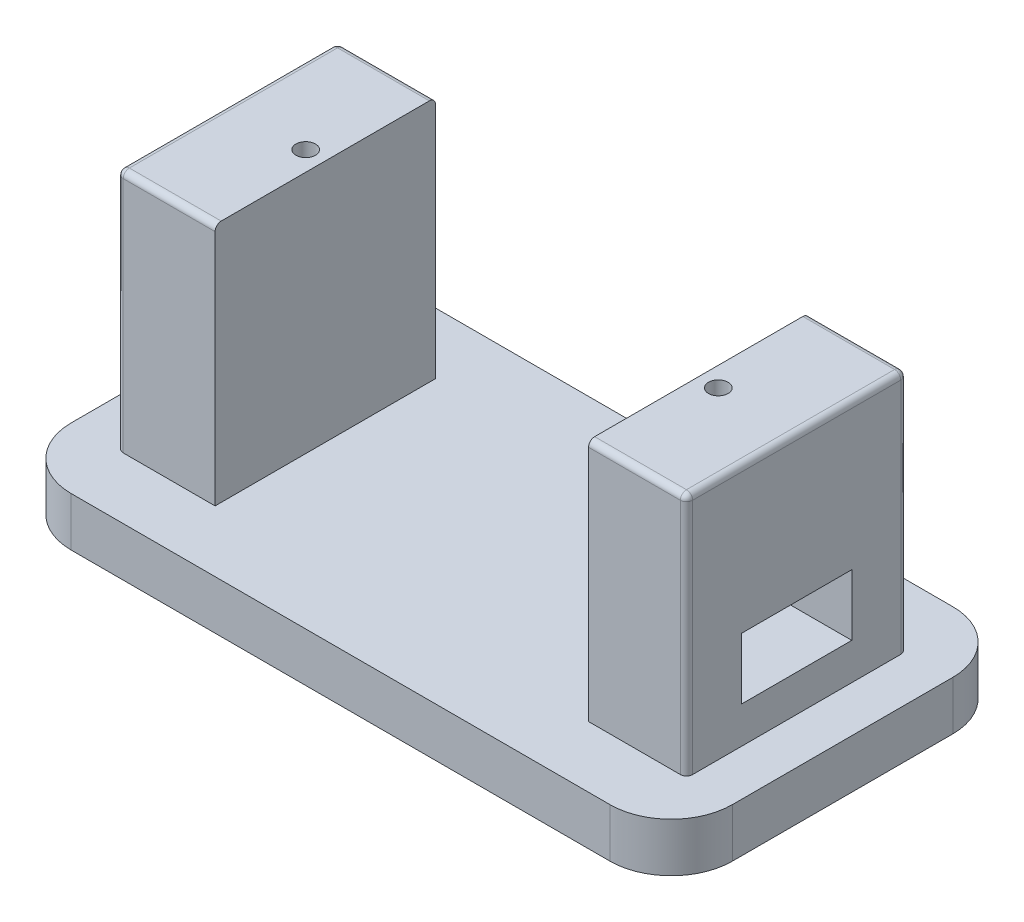
SolidWorks part; units mm, degrees
ref_plane "Front Plane" through (0, 0, 0) normal (0, 0, 1) x (1, 0, 0)
ref_plane "Top Plane" through (0, 0, 0) normal (0, 1, 0) x (1, 0, 0)
ref_plane "Right Plane" through (0, 0, 0) normal (1, 0, 0) x (0, 0, -1)
sketch "Sketch1" plane through (0, 0, 0) normal (0, 1, 0) x (1, 0, 0)
  line L1 (-27, 14) -> (27, 14)
  line L2 (-27, 14) -> (-27, -14)
  line L3 (-27, -14) -> (27, -14)
  line L4 (27, 14) -> (27, -14)
  line L5 (-27, 14) -> (27, -14) construction
  line L6 (-27, -14) -> (27, 14) construction
  point P0 (0, 0)
  dimension "D1" = 54
  dimension "D2" = 28
extrude "Boss-Extrude1" add sketch "Sketch1" along normal blind 4
sketch "Sketch3" plane through (0, 4, 0) normal (0, 1, 0) x (1, 0, 0)
  line L0 (0, -2.2) -> (0, 2.2) construction
  line L1 (-15.25, 11) -> (15.25, 11)
  line L2 (-15.25, 11) -> (-15.25, -11)
  line L3 (-15.25, -11) -> (15.25, -11)
  line L4 (15.25, 11) -> (15.25, -11)
  line L5 (-15.25, 11) -> (15.25, -11) construction
  line L6 (-15.25, -11) -> (15.25, 11) construction
  line L8 (27, 14) -> (-27, 14) construction
  point P0 (0, 0)
  dimension "D1" = 30.5
  dimension "D2" = 3
  dimension "D3" = 22
sketch "Sketch4" plane through (0, 4, 0) normal (0, 1, 0) x (1, 0, 0)
  line L0 (-27, -14) -> (27, -14) construction
  line L1 (-15.25, 9) -> (-23.25, 9)
  line L2 (-15.25, 9) -> (-15.25, -9)
  line L3 (-15.25, -9) -> (-23.25, -9)
  line L4 (-23.25, 9) -> (-23.25, -9)
  line L5 (-15.25, 11) -> (-15.25, -11) construction
  dimension "D1" = 18
  dimension "D2" = 8
  dimension "D3" = 5
extrude "Boss-Extrude3" add sketch "Sketch4" along normal blind 19.9
mirror "Mirror2" about plane through (0, 0, 0) normal (1, 0, 0) of "Boss-Extrude3"
fillet "Fillet1" radius 5 4 edges at (27, 2, 14) (27, 2, -14) (-27, 2, -14) (-27, 2, 14)
sketch "Sketch5" plane through (0, 23.9, 0) normal (0, 1, 0) x (1, 0, 0)
  line L0 (-15.25, 11) -> (-15.25, -11) construction
  circle A0 centre (-16.85, 0) radius 0.8
  dimension "D1" = 1.6
extrude "Cut-Extrude1" cut sketch "Sketch5" against normal blind 5
mirror "Mirror3" about plane through (0, 0, 0) normal (1, 0, 0) of "Cut-Extrude1"
sketch "Sketch6" plane through (23.25, 0, 0) normal (1, 0, 0) x (0, 0, -1)
  line L0 (-9, 23.9) -> (-9, 4) construction
  line L1 (-4.5, 11.9922) -> (4.5, 11.9922)
  line L2 (-4.5, 11.9922) -> (-4.5, 6.9922)
  line L3 (-4.5, 6.9922) -> (4.5, 6.9922)
  line L4 (4.5, 11.9922) -> (4.5, 6.9922)
  line L5 (-4.5, 11.9922) -> (4.5, 6.9922) construction
  line L6 (-4.5, 6.9922) -> (4.5, 11.9922) construction
  point P0 (0, 9.4922)
  dimension "D1" = 9
  dimension "D2" = 5
  dimension "D3" = 4.5
extrude "Cut-Extrude2" cut sketch "Sketch6" against normal blind 13
fillet "Fillet4" radius 0.5 6 edges at (-19.25, 23.9, -9) (-23.25, 23.9, 0) (-19.25, 23.9, 9) (19.25, 23.9, 9) (23.25, 23.9, 0) (19.25, 23.9, -9)
fillet "Fillet5" radius 0.5 8 edges at (23.1036, 23.7536, 8.8536) (23.1036, 23.7536, -8.8536) (-23.1036, 23.7536, 8.8536) (-23.1036, 23.7536, -8.8536) (23.25, 13.7, 9) (23.25, 13.7, -9) (-23.25, 13.7, 9) (-23.25, 13.7, -9)
